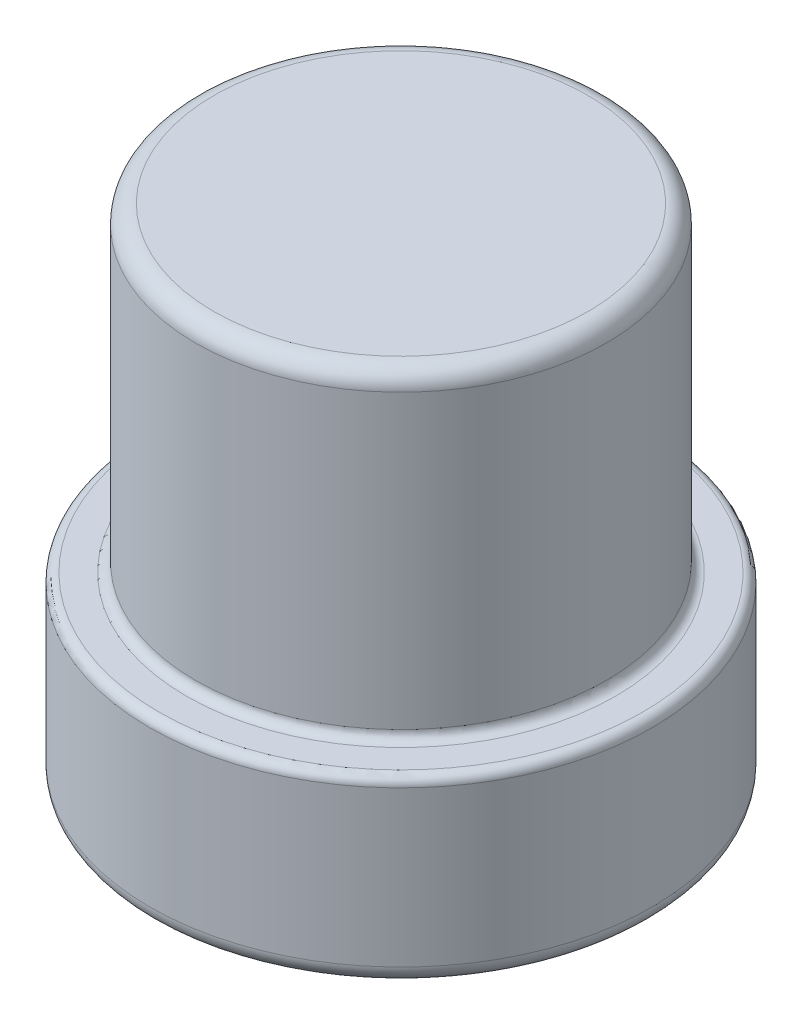
SolidWorks part; units mm, degrees
ref_plane "前视基准面" through (0, 0, 0) normal (0, 0, 1) x (1, 0, 0)
ref_plane "上视基准面" through (0, 0, 0) normal (0, 1, 0) x (1, 0, 0)
ref_plane "右视基准面" through (0, 0, 0) normal (1, 0, 0) x (0, 0, -1)
other "Configuration Table"
ref_axis "基准轴1" through (0, -46.8641, 0) along (0, 1, 0)
sketch "草图2" plane through (0, 0, 0) normal (0, 1, 0) x (1, 0, 0)
  circle A0 centre (0, 0) radius 5.5
  dimension "D1" = 11
extrude "凸台-拉伸1" add sketch "草图2" along normal blind 4
sketch "草图3" plane through (0, 4, 0) normal (0, 1, 0) x (1, 0, 0)
  circle A0 centre (0, 0) radius 4.5
  dimension "D1" = 9
extrude "凸台-拉伸2" add sketch "草图3" along normal blind 7
sketch "草图4" plane through (0, 0, 0) normal (0, -1, 0) x (1, 0, 0)
  circle A0 centre (0, 0) radius 3.5
  dimension "D1" = 7
extrude "切除-拉伸1" cut sketch "草图4" against normal blind 4.5
fillet "圆角1" radius 0.4 3 edges at (0, 0, 5.5) (0, 0, -3.5) (0, 11, 4.5)
fillet "圆角2" radius 0.2 2 edges at (0, 4, 5.5) (0, 4, 4.5)
